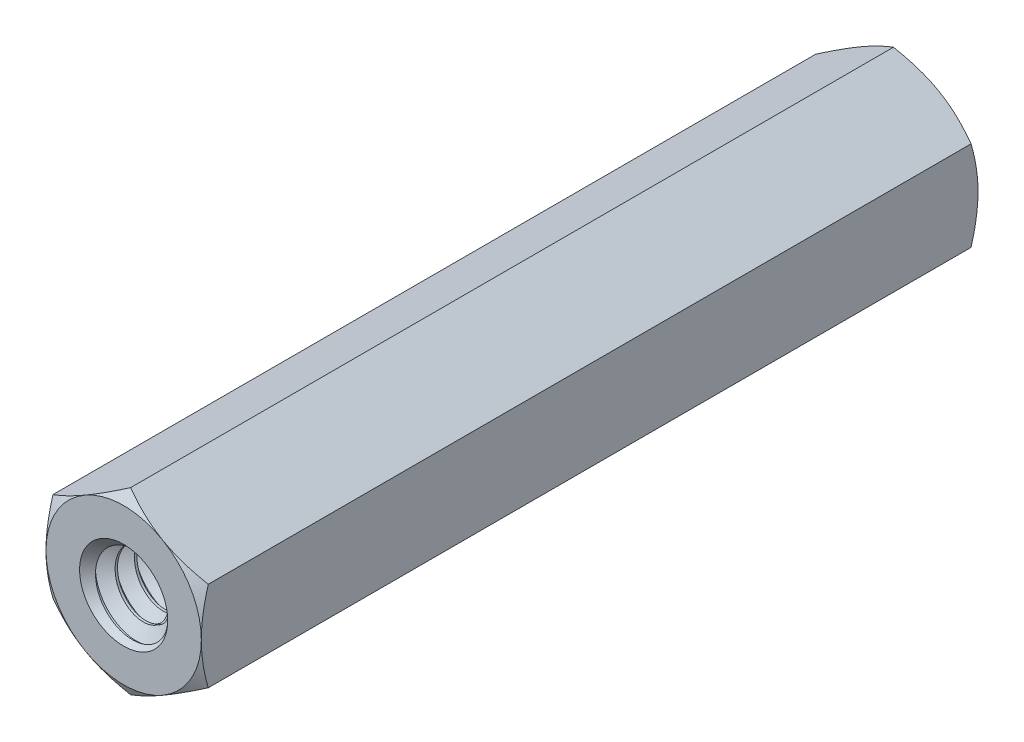
SolidWorks part; units mm, degrees
ref_plane "Front Plane" through (0, 0, 0) normal (0, 0, 1) x (1, 0, 0)
ref_plane "Top Plane" through (0, 0, 0) normal (0, 1, 0) x (1, 0, 0)
ref_plane "Right Plane" through (0, 0, 0) normal (1, 0, 0) x (0, 0, -1)
sketch "Sketch3" plane through (0, 0, 0) normal (1, 0, 0) x (0, 0, -1)
  line L0 (-15.875, 0) -> (15.875, 0) construction
  line L1 (0, 3.175) -> (0, -3.175) construction
  line L2 (-15.875, 1.7526) -> (-15.875, -1.7526) construction
  point P2 (6.35, 0)
  point P3 (-6.35, 0)
  dimension "Length" = 31.75
  dimension "Min Thread Length" = 9.525
  dimension "D1" = 9.525
  dimension "Thread Dia" = 3.5052
  dimension "Hex" = 6.35
sketch "Sketch1" plane through (0, 0, 0) normal (0, 0, 1) x (1, 0, 0)
  line L1 (0, 3.6662) -> (-3.175, 1.8331)
  line L2 (-3.175, 1.8331) -> (-3.175, -1.8331)
  line L3 (-3.175, -1.8331) -> (0, -3.6662)
  line L4 (0, -3.6662) -> (3.175, -1.8331)
  line L5 (3.175, -1.8331) -> (3.175, 1.8331)
  line L6 (3.175, 1.8331) -> (0, 3.6662)
  circle A0 centre (0, 0) radius 3.175 construction
  circle A1 centre (0, 0) radius 1.7526
extrude "Extrude1" add sketch "Sketch1" along normal up to vertex (15.875 mm away) and the other way up to vertex (15.875 mm away) up to point (0, 0, 15.875) other way up to point (0, 0, -15.875)
sketch "Sketch11" plane through (0, 0, -15.875) normal (0, 0, -1) x (-1, 0, 0)
  circle A0 centre (0, 0) radius 1.7526 construction
  circle A1 centre (0, 0) radius 1.7526
curve "Helix/Spiral1" pitch 0.7937 height 32.5437 turns 41 parameters "Pitch"=0.7937
sketch "Sketch12" plane through (0, 0, 0) normal (1, 0, 0) x (0, 0, -1)
  line L0 (16.5695, 1.7526) -> (15.875, 1.7526)
  line L1 (16.5695, 1.7526) -> (16.2719, 1.237)
  line L2 (16.2719, 1.237) -> (16.1727, 1.237)
  line L3 (16.1727, 1.237) -> (15.875, 1.7526)
  line L4 (16.2223, 1.237) -> (16.2223, 1.7526) construction
  line L5 (16.4207, 1.4948) -> (16.0238, 1.4948) construction
  dimension "D1" = 0.0992
  dimension "D2" = 0.3969
  dimension "D3" = 60
sweep "Sweep1" add profiles "Sketch12" path "Helix/Spiral1"
sketch "Sketch6" plane through (0, 0, -15.875) normal (0, 0, -1) x (-1, 0, 0)
  line L6 (0, 3.6662) -> (-3.175, 1.8331)
  line L7 (-3.175, 1.8331) -> (-3.175, -1.8331)
  line L8 (-3.175, -1.8331) -> (0, -3.6662)
  line L9 (0, -3.6662) -> (3.175, -1.8331)
  line L10 (3.175, -1.8331) -> (3.175, 1.8331)
  line L11 (3.175, 1.8331) -> (0, 3.6662)
  line L12 (0, 3.6662) -> (-3.175, 1.8331)
  line L13 (-3.175, 1.8331) -> (-3.175, -1.8331)
  line L14 (-3.175, -1.8331) -> (0, -3.6662)
  line L15 (0, -3.6662) -> (3.175, -1.8331)
  line L16 (3.175, -1.8331) -> (3.175, 1.8331)
  line L17 (3.175, 1.8331) -> (0, 3.6662)
  dimension "D1" = 0
extrude "Extrude2" cut sketch "Sketch6" along normal through all
sketch "Sketch7" plane through (0, 0, -15.875) normal (0, 0, -1) x (-1, 0, 0)
  circle A2 centre (0, 0) radius 1.8034
  circle A3 centre (0, 0) radius 1.8034
  dimension "D1" = 0.0508
extrude "Extrude3" cut sketch "Sketch7" against normal through all draft 43
sketch "Sketch8" plane through (0, 0, -15.875) normal (0, 0, -1) x (-1, 0, 0)
  circle A0 centre (0, 0) radius 3.175 construction
  circle A1 centre (0, 0) radius 3.175
extrude "Extrude4" cut sketch "Sketch8" against normal through all draft 60 flip side to cut
mirror "Mirror1" about plane through (0, 0, 0) normal (0, 0, 1) of "Extrude2", "Extrude3", "Extrude4"
sketch "Sketch9" plane through (0, 0, 0) normal (1, 0, 0) x (0, 0, -1)
  line L1 (-6.35, 1.8034) -> (6.35, 1.8034)
  line L2 (-6.35, 1.8034) -> (-6.35, 0)
  line L3 (-6.35, 0) -> (6.35, 0)
  line L4 (6.35, 1.8034) -> (6.35, 0)
  line L7 (-15.875, 0) -> (15.875, 0) construction
revolve "Revolve" add sketch "Sketch9" angle 360 about L0
sketch "Sketch10" plane through (0, 0, 0) normal (1, 0, 0) x (0, 0, -1)
  line L0 (15.875, 1.7526) -> (6.35, 1.7526)
  line L1 (-15.875, 1.7526) -> (-6.35, 1.7526)
  line L2 (6.35, 1.7526) -> (6.35, -1.7526)
  line L3 (-15.875, -1.8034) -> (-6.35, -1.8034)
  line L4 (-6.35, 1.7526) -> (-6.35, -1.8034)
  line L5 (6.35, -1.7526) -> (15.875, -1.7526)
equation "\"D1@Sketch3\" = \"Min Thread Length@Sketch3\""
equation "\"D3@Helix/Spiral1\" = \"Length@Sketch3\"+\"Pitch@Helix/Spiral1\""
equation "\"D1@Sketch12\" = \"Pitch@Helix/Spiral1\"*.125"
equation "\"D2@Sketch12\" = \"Pitch@Helix/Spiral1\"*.5"
